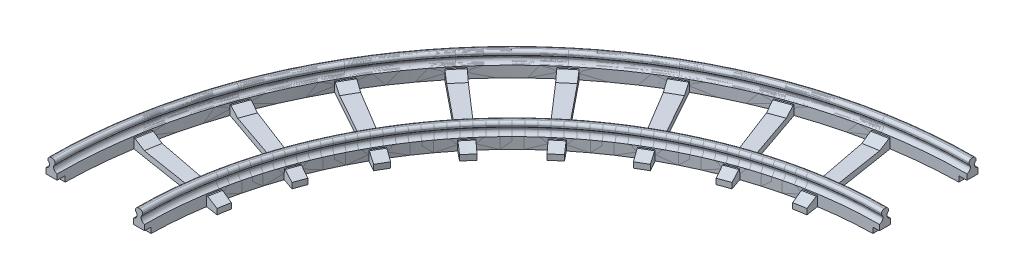
SolidWorks part; units mm, degrees
other "标注1"
sketch "草图3" plane through (-22.25, 4, -10) normal (-0.231, 0.6469, -0.7268) x (-0.9696, -0.2151, 0.1167)
ref_plane "前视基准面" through (0, 0, 0) normal (0, 0, 1) x (1, 0, 0)
ref_plane "上视基准面" through (0, 0, 0) normal (0, 1, 0) x (1, 0, 0)
ref_plane "右视基准面" through (0, 0, 0) normal (1, 0, 0) x (0, 0, -1)
other "Configuration Table"
sketch "草图4" plane through (0, 0, 0) normal (0, 0, 1) x (1, 0, 0)
  line L0 (0, 0) -> (31.5, 0) construction
  line L1 (0.75, -1.5) -> (1.25, -1.5)
  line L3 (0, 0) -> (1.25, 0)
  line L4 (1.25, -1.5) -> (1.25, 0)
  line L5 (0, 0) -> (-1.25, 0)
  line L10 (0.75, -1.5) -> (0.75, -4)
  line L11 (-0.75, -1.5) -> (-1.25, -1.5)
  line L12 (0.75, -4) -> (2, -4)
  line L14 (0, -8) -> (2, -8)
  line L15 (2, -4) -> (2, -8)
  line L16 (-1.25, 0) -> (-1.25, -1.5)
  line L20 (-0.75, -1.5) -> (-0.75, -4)
  line L21 (-0.75, -4) -> (-2, -4)
  line L23 (0, -8) -> (-2, -8)
  line L24 (-2, -4) -> (-2, -8)
  line L25 (31.5, 0) -> (32.75, 0)
  line L26 (30.25, 0) -> (31.5, 0)
  line L27 (30.25, 0) -> (30.25, -1.5)
  line L28 (30.25, -1.5) -> (30.75, -1.5)
  line L31 (30.75, -1.5) -> (30.75, -4)
  line L34 (29.5, -4) -> (30.75, -4)
  line L35 (29.5, -4) -> (29.5, -8)
  line L36 (29.5, -8) -> (31.5, -8)
  line L39 (32.25, -1.5) -> (32.75, -1.5)
  line L40 (32.75, 0) -> (32.75, -1.5)
  line L42 (32.25, -1.5) -> (32.25, -4)
  line L45 (32.25, -4) -> (33.5, -4)
  line L47 (31.5, -8) -> (33.5, -8)
  line L48 (33.5, -4) -> (33.5, -8)
  point P0 (0, 0)
  point P2 (15.75, 0)
  dimension "D1" = 1.25
  dimension "D4" = 2.5
sketch "草图6" plane through (0, 0, 0) normal (0, 0, 1) x (1, 0, 0)
  line L0 (165.75, 3.8535) -> (165.75, -12.2756)
  dimension "D1" = 150
revolve "旋转1" add sketch "草图4" angle 10 about L0
fillet "圆角1" radius 1.5 2 edges at (1.3779, -4, -14.3807) (-0.1164, -4, -14.5114)
fillet "圆角2" radius 1.5 2 edges at (31.2637, -4, -11.766) (32.758, -4, -11.6353)
fillet "圆角3" radius 1 4 edges at (33.2561, 0, -11.5917) (30.7656, 0, -11.8096) (31.2637, -1.5, -11.766) (32.758, -1.5, -11.6353)
fillet "圆角4" radius 1 4 edges at (1.876, 0, -14.3371) (-0.1164, -1.5, -14.5114) (1.3779, -1.5, -14.3807) (-0.6145, 0, -14.555)
sketch "草图7" plane through (0, 0, 0) normal (0, 0, 1) x (1, 0, 0)
  line L1 (-2, -8) -> (2, -8)
  line L2 (-2, -8) -> (-2, -6)
  line L3 (-2, -6) -> (2, -6)
  line L4 (2, -8) -> (2, -6)
  line L5 (33.5, -8) -> (33.5, -4) construction
  line L6 (29.5, -8) -> (33.5, -8)
  line L7 (29.5, -8) -> (29.5, -6)
  line L8 (29.5, -6) -> (33.5, -6)
  line L9 (33.5, -8) -> (33.5, -6)
  line L10 (2, -8) -> (2, -4) construction
  dimension "D1" = 2
sketch "草图9" plane through (0, 0, 0) normal (0, 1, 0) x (1, 0, 0)
  line L0 (29.5, 0) -> (2, 0)
  line L1 (-2, 0) -> (2, 0) construction
  line L2 (4.4877, 28.4349) -> (31.5699, 23.6596)
  line L3 (18.0288, 26.0472) -> (15.75, 0)
  arc A0 (4.4877, 28.4349) -> (2, 0) centre (165.75, 0) ccw construction
  arc A1 (31.5699, 23.6596) -> (29.5, 0) centre (165.75, 0) ccw construction
  point P20 (165.75, 0)
  dimension "D1" = 10
  dimension "D2" = 26.1467
revolve "切除-旋转1" cut sketch "草图7" angle 1 about L0
sketch "草图10" plane through (0, -6, 0) normal (0, -1, 0) x (1, 0, 0)
  line L0 (-1.9936, -1.4639) -> (2.0062, -1.429) construction
  line L2 (2.0062, -1.429) -> (29.5052, -1.189) construction
  line L3 (29.5052, -1.189) -> (33.505, -1.1541) construction
  circle A1 centre (0.0063, -1.4464) radius 0.4
  circle A2 centre (31.5051, -1.1715) radius 0.4
  arc A3 (-2, 0) -> (-1.9745, -2.9276) centre (165.75, 0) ccw construction
  arc A4 (2, 0) -> (2.0249, -2.8578) centre (165.75, 0) ccw construction
  arc A5 (29.5, 0) -> (29.5208, -2.3779) centre (165.75, 0) ccw construction
  arc A6 (33.5, 0) -> (33.5201, -2.3081) centre (165.75, 0) ccw construction
  dimension "D1" = 0.8
extrude "切除-拉伸1" cut sketch "草图10" against normal blind 2
sketch "草图11" plane through (4.998, 0, -28.3449) normal (0.1736, 0, -0.9848) x (-0.9848, 0, -0.1736)
  line L0 (-26.9819, -4.5) -> (-26.4819, -4.5)
  line L1 (-26.9819, -4) -> (-26.9819, -8) construction
  line L2 (-26.4819, -4.5) -> (-22.4819, -6)
  line L3 (-22.4819, -6) -> (-3.9819, -6)
  line L4 (-3.9819, -6) -> (0.0181, -4.5)
  line L5 (0.0181, -4.5) -> (0.5181, -4.5)
  line L6 (0.5181, -8) -> (0.5181, -4) construction
  line L7 (0.5181, -4.5) -> (4.5181, -4.5)
  line L8 (4.5181, -4) -> (4.5181, -8) construction
  line L9 (4.5181, -4.5) -> (5.0181, -4.5)
  line L10 (5.0181, -4.5) -> (9.0181, -6)
  line L11 (9.0181, -6) -> (9.0181, -8)
  line L13 (-35.4819, -8) -> (-35.4819, -6)
  line L14 (-35.4819, -6) -> (-31.4819, -4.5)
  line L15 (-31.4819, -4.5) -> (-30.9819, -4.5)
  line L16 (-30.9819, -8) -> (-30.9819, -4) construction
  line L17 (-30.9819, -4.5) -> (-26.9819, -4.5)
  line L19 (-35.4819, -8) -> (-30.9819, -8)
  line L20 (-30.9819, -8) -> (-26.9819, -8)
  line L21 (-26.9819, -8) -> (0.5181, -8)
  line L22 (0.5181, -8) -> (4.5181, -8)
  line L23 (4.5181, -8) -> (9.0181, -8)
  dimension "D1" = 0.5
  dimension "D2" = 4.5
  dimension "D3" = 3.5
  dimension "D4" = 2
revolve "旋转2" add sketch "草图11" angle 1 about L0
mirror "镜向1"
pattern_circular "阵列(圆周)1" count 8 every 10 about axis through (165.75, 0, 0) along (0, 1, 0) of bodies 229
